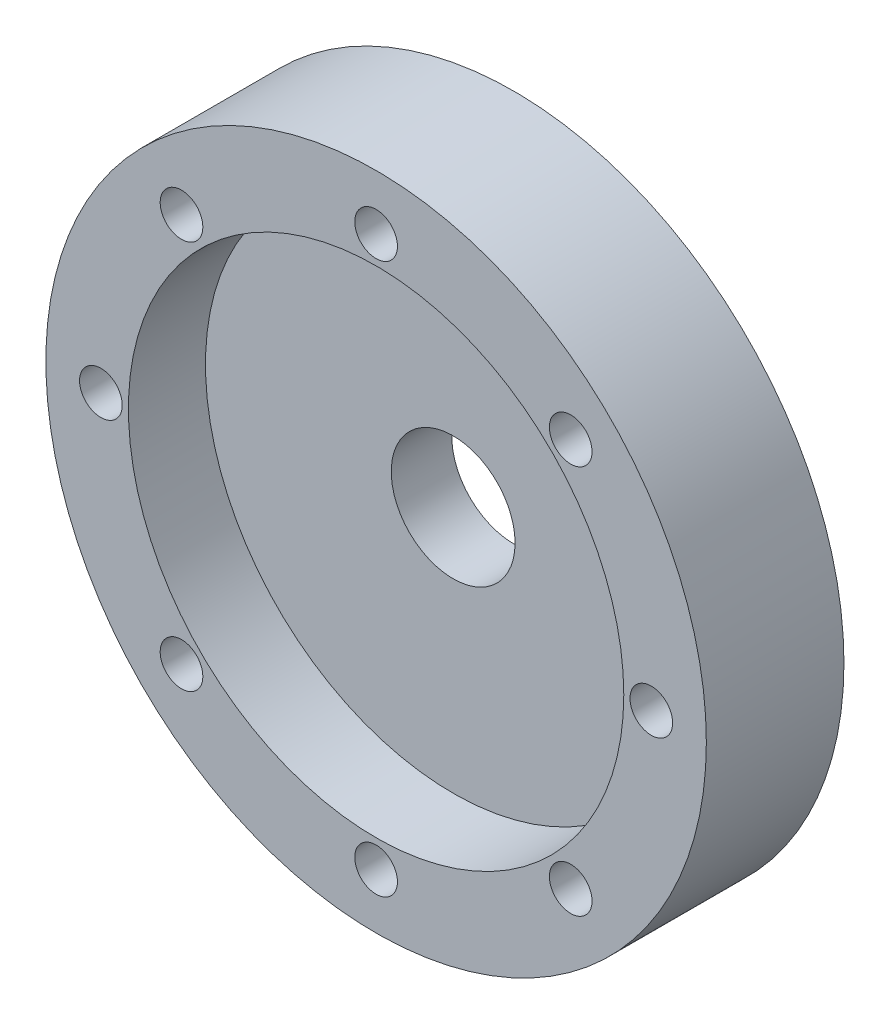
SolidWorks part; units mm, degrees
ref_plane "Front Plane" through (0, 0, 0) normal (0, 0, 1) x (1, 0, 0)
ref_plane "Top Plane" through (0, 0, 0) normal (0, 1, 0) x (1, 0, 0)
ref_plane "Right Plane" through (0, 0, 0) normal (1, 0, 0) x (0, 0, -1)
ref_axis "Axis1" through (0, 0, 5.5) along (0, 0, -1)
sketch "Sketch6" plane through (0, 0, 0) normal (0, 0, 1) x (1, 0, 0)
  line L0 (0, 0) -> (0, 20) construction
  circle A0 centre (0, 0) radius 24
  circle A1 centre (0, 20) radius 1.55
  circle A2 centre (14.1421, 14.1421) radius 1.55
  circle A3 centre (20, 0) radius 1.55
  circle A4 centre (14.1421, -14.1421) radius 1.55
  circle A5 centre (0, -20) radius 1.55
  circle A6 centre (-14.1421, -14.1421) radius 1.55
  circle A7 centre (-20, 0) radius 1.55
  circle A8 centre (-14.1421, 14.1421) radius 1.55
  circle A9 centre (0, 0) radius 4.5
  point P21 (0, 0)
  dimension "D1" = 8
extrude "Boss-Extrude1" add sketch "Sketch6" along normal blind 10
sketch "Sketch8" plane through (0, 0, 0) normal (0, 0, -1) x (-1, 0, 0)
  line L0 (0, 20) -> (0, 0) construction
  circle A0 centre (0, 20) radius 3.5
  circle A1 centre (14.1421, 14.1421) radius 3.5
  circle A2 centre (20, 0) radius 3.5
  circle A3 centre (14.1421, -14.1421) radius 3.5
  circle A4 centre (0, -20) radius 3.5
  circle A5 centre (-14.1421, -14.1421) radius 3.5
  circle A6 centre (-20, 0) radius 3.5
  circle A7 centre (-14.1421, 14.1421) radius 3.5
  point P20 (0, 0)
  dimension "D1" = 8
extrude "Cut-Extrude6" cut sketch "Sketch8" against normal blind 3
sketch "Sketch9" plane through (0, 0, 10) normal (0, 0, 1) x (1, 0, 0)
  circle A0 centre (0, 0) radius 18
extrude "Cut-Extrude7" cut sketch "Sketch9" against normal blind 5.6
